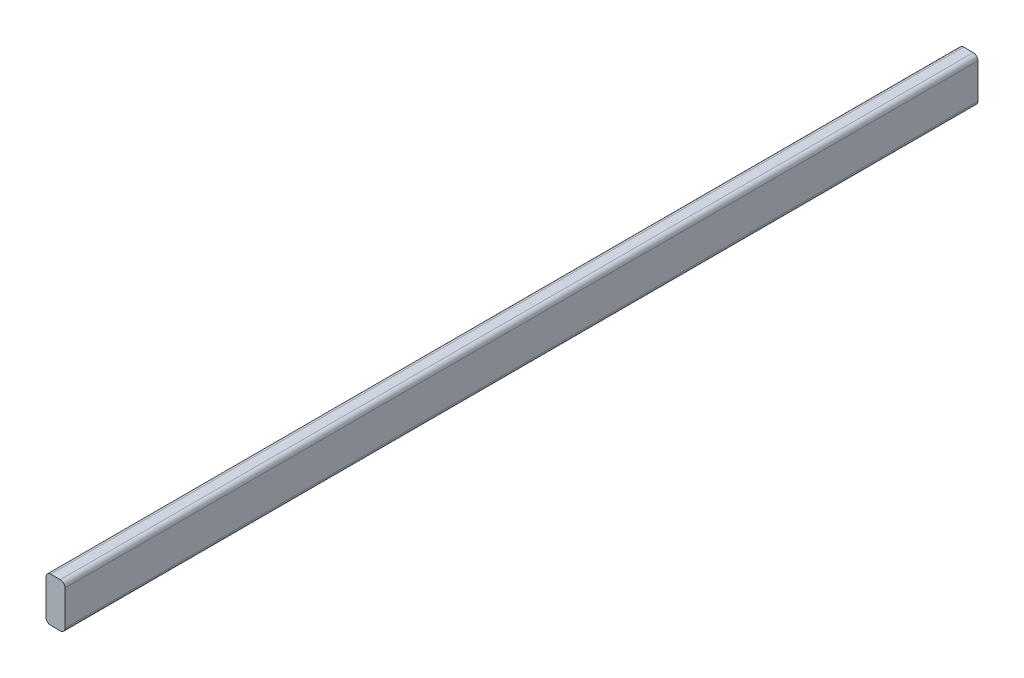
SolidWorks part; units mm, degrees
ref_plane "Front Plane" through (0, 0, 0) normal (0, 0, 1) x (1, 0, 0)
ref_plane "Top Plane" through (0, 0, 0) normal (0, 1, 0) x (1, 0, 0)
ref_plane "Right Plane" through (0, 0, 0) normal (1, 0, 0) x (0, 0, -1)
sketch "Sketch1" plane through (0, 0, 0) normal (0, 0, 1) x (1, 0, 0)
  line L0 (-9.525, 22.225) -> (-9.525, -22.225) construction
  line L1 (-9.525, 22.225) -> (9.525, 22.225) construction
  line L2 (-9.525, 0) -> (0, 0) construction
  line L3 (0, 0) -> (0, 22.225) construction
  dimension "Thickness" = 19.05
  dimension "Width" = 44.45
ref_plane "Plane1" through (-9.525, 22.225, 0) normal (0, -1, 0) x (-1, 0, 0)
sketch "Sketch2" plane through (-9.525, 22.225, 0) normal (0, 1, 0) x (1, 0, 0)
  line L0 (9.525, -457.2) -> (9.525, 457.2) construction
  point P2 (9.525, -390.525)
  point P3 (9.525, 390.525)
  dimension "Length" = 914.4
  dimension "D1" = 66.675
  dimension "D2" = 66.675
sketch "Sketch3" plane through (0, 0, 0) normal (0, 0, 1) x (1, 0, 0)
  line L1 (-9.525, -22.225) -> (9.525, -22.225)
  line L2 (-9.525, -22.225) -> (-9.525, 22.225)
  line L3 (-9.525, 22.225) -> (9.525, 22.225)
  line L4 (9.525, -22.225) -> (9.525, 22.225)
  line L5 (0, 22.225) -> (0, -22.225) construction
  line L6 (-9.525, 0) -> (9.525, 0) construction
  line L7 (-9.525, 0) -> (0, 0) construction
extrude "Boss-Extrude1" add sketch "Sketch3" along normal up to vertex (457.2 mm away) and the other way up to vertex (457.2 mm away) up to point (0, 22.225, 457.2) other way up to point (0, 22.225, -457.2)
fillet "Fillet1" radius 4.7625 4 edges at (9.525, -22.225, 0) (-9.525, -22.225, 0) (9.525, 22.225, 0) (-9.525, 22.225, 0)
equation "\"D1@Sketch2\"=\"Width@Sketch1\"*1.5"
equation "\"D2@Sketch2\"=\"D1@Sketch2\""
equation "\"D1@Fillet1\"=\"Thickness@Sketch1\"/4"
